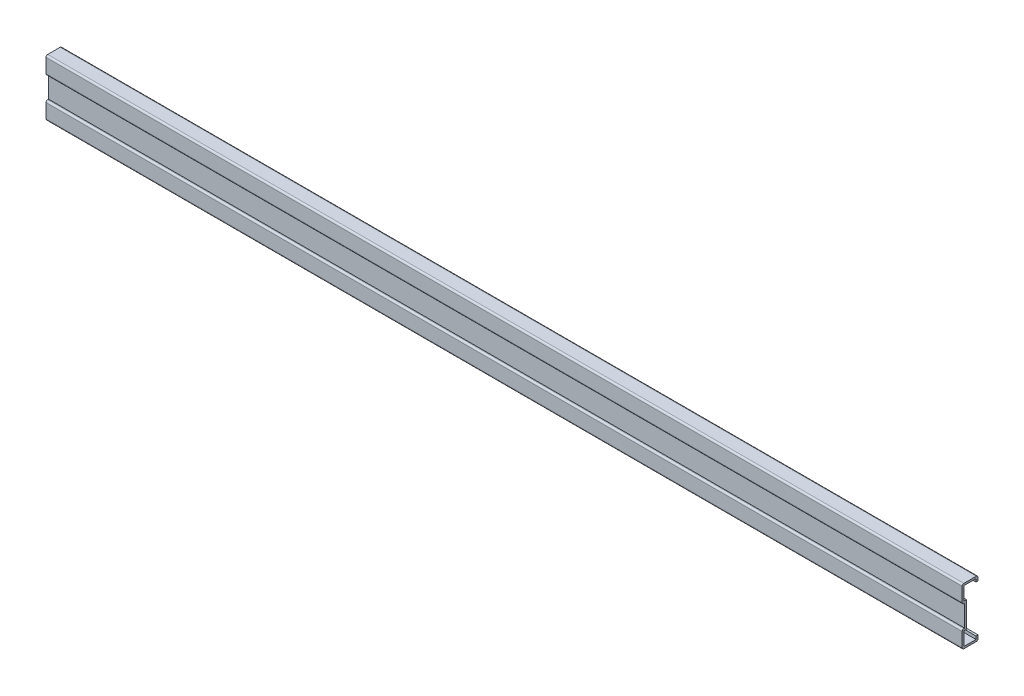
SolidWorks part; units mm, degrees
ref_plane "Спереди" through (0, 0, 0) normal (0, 0, 1) x (1, 0, 0)
ref_plane "Сверху" through (0, 0, 0) normal (0, 1, 0) x (1, 0, 0)
ref_plane "Справа" through (0, 0, 0) normal (1, 0, 0) x (0, 0, -1)
sketch "Эскиз1" plane through (0, 0, 0) normal (1, 0, 0) x (0, 0, -1)
  line L0 (0, 6.5) -> (0, -6.5)
  line L1 (-12.4481, 0) -> (26.4522, 0) construction
  line L2 (0, -6.5) -> (-0.5, -6.5)
  line L3 (-1.5, -7.5) -> (-1.5, -16)
  line L4 (-0.5, -17) -> (7, -17)
  line L5 (8, -16) -> (8, -14)
  line L6 (8, 16) -> (8, 14)
  line L7 (-0.5, 17) -> (7, 17)
  line L8 (-1.5, 7.5) -> (-1.5, 16)
  line L9 (0, 6.5) -> (-0.5, 6.5)
  arc A0 (7, -17) -> (8, -16) centre (7, -16) ccw
  arc A1 (-1.5, -7.5) -> (-0.5, -6.5) centre (-0.5, -7.5) cw
  arc A2 (-1.5, 16) -> (-0.5, 17) centre (-0.5, 16) cw
  arc A3 (-1.5, -16) -> (-0.5, -17) centre (-0.5, -16) ccw
  arc A4 (-1.5, 7.5) -> (-0.5, 6.5) centre (-0.5, 7.5) ccw
  arc A5 (7, 17) -> (8, 16) centre (7, 16) cw
  point P14 (0, 0)
  point P16 (8, -17)
  point P20 (0, 0)
  point P26 (-1.5, -17)
  point P30 (0, 0)
  dimension "D1" = 1
  dimension "D2" = 1
extrude "Вытянуть-Тонкостенный3" add sketch "Эскиз1" along normal blind 550 thin thin type one direction wall 1.2
